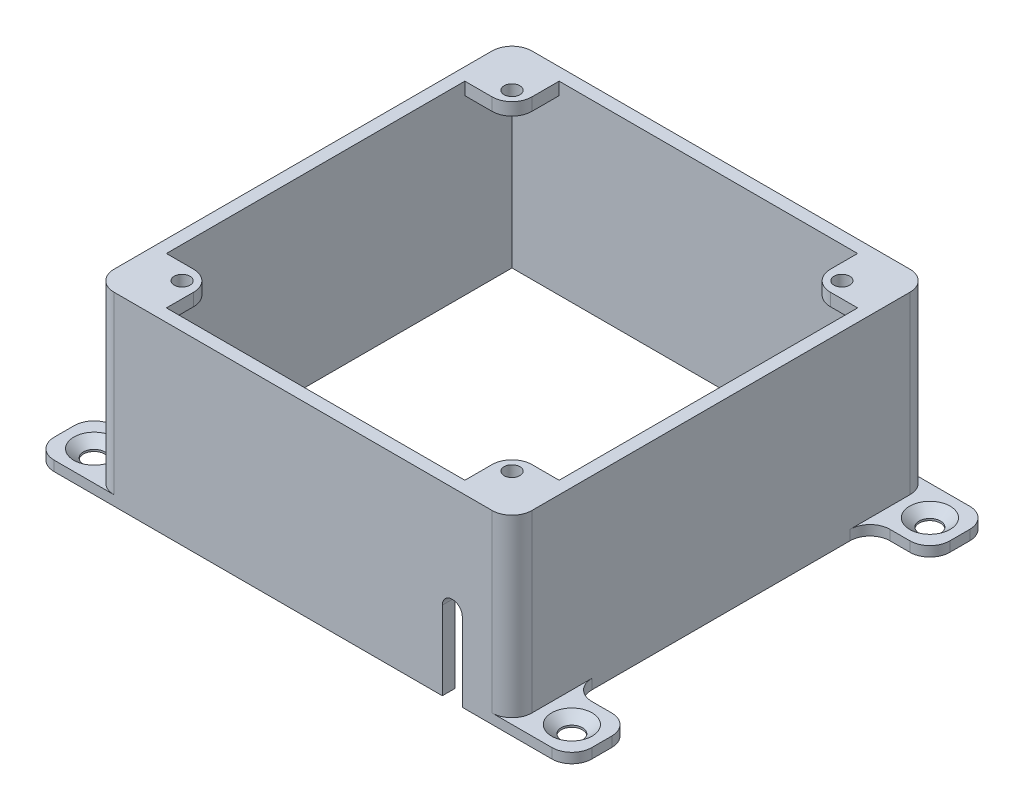
SolidWorks part; units mm, degrees
note: The reader was unsure of these and kept them because the rebuilt part matched: shared geometry of "Sketch1<3>".
ref_plane "Front Plane" through (0, 0, 0) normal (0, 0, 1) x (1, 0, 0)
ref_plane "Top Plane" through (0, 0, 0) normal (0, 1, 0) x (1, 0, 0)
ref_plane "Right Plane" through (0, 0, 0) normal (1, 0, 0) x (0, 0, -1)
sketch "Sketch1" plane through (0, 0, 0) normal (0, 1, 0) x (1, 0, 0)
  line L0 (66.5, 66.5) -> (-66.5, 66.5)
  line L1 (62.5, -62.5) -> (-62.5, -62.5)
  line L2 (62.5, -62.5) -> (62.5, 62.5)
  line L3 (62.5, 62.5) -> (-62.5, 62.5)
  line L4 (-62.5, -62.5) -> (-62.5, 62.5)
  line L5 (62.5, -62.5) -> (-62.5, 62.5) construction
  line L6 (62.5, 62.5) -> (-62.5, -62.5) construction
  line L7 (-66.5, -66.5) -> (-66.5, 66.5)
  line L8 (66.5, -66.5) -> (-66.5, -66.5)
  line L9 (66.5, -66.5) -> (66.5, 66.5)
  line L10 (0, 0) -> (0, 50000) construction
  line L11 (-66.5, 66.5) -> (-85.55, 66.5)
  line L12 (-66.5, 66.5) -> (-66.5, 47.45)
  line L13 (-66.5, 47.45) -> (-85.55, 47.45)
  line L14 (-85.55, 66.5) -> (-85.55, 47.45)
  line L15 (0, 0) -> (50000, 0) construction
  line L16 (66.5, 47.45) -> (85.55, 47.45)
  line L17 (85.55, 66.5) -> (85.55, 47.45)
  line L18 (66.5, 66.5) -> (85.55, 66.5)
  line L19 (66.5, 66.5) -> (66.5, 47.45)
  line L20 (66.5, -66.5) -> (85.55, -66.5)
  line L21 (85.55, -66.5) -> (85.55, -47.45)
  line L22 (66.5, -47.45) -> (85.55, -47.45)
  line L23 (66.5, -66.5) -> (66.5, -47.45)
  line L24 (-66.5, -47.45) -> (-85.55, -47.45)
  line L25 (-85.55, -66.5) -> (-85.55, -47.45)
  line L26 (-66.5, -66.5) -> (-85.55, -66.5)
  line L27 (-66.5, -66.5) -> (-66.5, -47.45)
  point P0 (0, 0)
  dimension "D1" = 125
  dimension "D3" = 19.05
  dimension "D4" = 19.05
  dimension "D2" = 4
extrude "Boss-Extrude1" add sketch "Sketch1" along normal blind 55 contours L8 L9 L0 L7 L1 L4 L3 L2
extrude "Boss-Extrude2" add sketch "Sketch1<3>" along normal blind 3.175 contours L11 L14 L13 L7 | L26 L7 L24 L25 | L22 L9 L20 L21 | L18 L9 L16 L17
sketch "Sketch1<3>" plane through (0, 0, 0) normal (0, 1, 0) x (1, 0, 0) same geometry as "Sketch1"
sketch "Sketch2" plane through (0, 55, 0) normal (0, 1, 0) x (1, 0, 0)
  line L0 (0, 0) -> (0, 50000) construction
  line L1 (-62.5, 62.5) -> (-47.5, 62.5) construction
  line L2 (-62.5, 62.5) -> (-62.5, 47.5) construction
  line L3 (-62.5, 47.5) -> (-47.5, 47.5)
  line L4 (-47.5, 62.5) -> (-47.5, 47.5)
  line L5 (0, 0) -> (50000, 0) construction
  line L6 (62.5, 47.5) -> (47.5, 47.5)
  line L7 (47.5, 62.5) -> (47.5, 47.5)
  line L8 (62.5, 62.5) -> (47.5, 62.5) construction
  line L9 (62.5, 62.5) -> (62.5, 47.5) construction
  line L10 (62.5, -62.5) -> (62.5, -47.5) construction
  line L11 (62.5, -62.5) -> (47.5, -62.5) construction
  line L12 (47.5, -62.5) -> (47.5, -47.5)
  line L13 (62.5, -47.5) -> (47.5, -47.5)
  line L14 (-62.5, -47.5) -> (-47.5, -47.5)
  line L15 (-47.5, -62.5) -> (-47.5, -47.5)
  line L16 (-62.5, -62.5) -> (-47.5, -62.5) construction
  line L17 (-62.5, -62.5) -> (-62.5, -47.5) construction
  line L18 (-62.5, 47.5) -> (-62.5, -47.5)
  line L19 (52.5, -52.5) -> (-52.5, -52.5) construction
  line L20 (52.5, -52.5) -> (52.5, 52.5) construction
  line L21 (52.5, 52.5) -> (-52.5, 52.5) construction
  line L22 (-52.5, -52.5) -> (-52.5, 52.5) construction
  line L23 (52.5, -52.5) -> (-52.5, 52.5) construction
  line L24 (52.5, 52.5) -> (-52.5, -52.5) construction
  line L25 (-47.5, -62.5) -> (47.5, -62.5)
  line L26 (62.5, -47.5) -> (62.5, 47.5)
  line L27 (47.5, 62.5) -> (-47.5, 62.5)
  line L28 (66.5, -66.5) -> (66.5, 66.5) construction
  line L29 (66.5, -66.5) -> (-66.5, -66.5) construction
  line L30 (-66.5, -66.5) -> (-66.5, 66.5) construction
  line L31 (66.5, 66.5) -> (-66.5, 66.5) construction
  line L32 (66.5, -66.5) -> (66.5, 66.5)
  line L33 (66.5, -66.5) -> (-66.5, -66.5)
  line L34 (-66.5, -66.5) -> (-66.5, 66.5)
  line L35 (66.5, 66.5) -> (-66.5, 66.5)
  circle A0 centre (-52.5, 52.5) radius 2.5
  circle A1 centre (52.5, 52.5) radius 2.5
  circle A2 centre (52.5, -52.5) radius 2.5
  circle A3 centre (-52.5, -52.5) radius 2.5
  point P22 (0, 0)
  dimension "D3" = 5
  dimension "D1" = 15
  dimension "D2" = 105
extrude "Boss-Extrude3" add sketch "Sketch2" along normal blind 4 contours L3 L4 L27 L7 L6 L26 L13 L12 L25 L15 L14 L18
sketch "Sketch3" plane through (0, 3.175, 0) normal (0, 1, 0) x (1, 0, 0)
  line L0 (-85.55, -56.975) -> (49914.45, -56.975) construction
  line L1 (-85.55, -66.5) -> (-85.55, -47.45) construction
  line L2 (-76.025, -47.45) -> (-76.025, -50047.45) construction
  line L3 (-66.5, -47.45) -> (-85.55, -47.45) construction
  point P4 (-85.55, -56.975)
  point P10 (-76.025, -56.975)
  point P13 (-76.025, -47.45)
hole_wizard "CSK for 1/4 Flat Head Machine Screw (100)1" positions "Sketch3" profile "Sketch5" countersink size "1/4" standard "ANSI Inch"
sketch "Sketch5" plane through (-76.025, 3.175, 56.975) normal (1, 0, 0) x (0, 0, 1)
  line L0 (0, 0) -> (0, 3.175)
  line L1 (0, 3.175) -> (3.3782, 3.175)
  line L2 (3.3782, 3.175) -> (3.3782, 2.5682)
  line L3 (3.3782, 2.5682) -> (6.4389, 0)
  line L5 (6.4389, 0) -> (0, 0)
  line L6 (-3.3782, 2.5682) -> (-6.4389, 0) construction
  line L11 (0, -6.35) -> (0, 107.95) construction
  dimension "Thru Hole Dia." = 6.7564
  dimension "Thru Hole Depth" = 3.175
  dimension "Near C'Sink Dia." = 12.8778
  dimension "Near C'Sink Angle" = 100
mirror "Mirror1" about plane through (0, 0, 0) normal (0, 0, 1) of "CSK for 1/4 Flat Head Machine Screw (100)1" second plane through (0, 0, 0) second plane normal (1, 0, 0)
fillet "Fillet1" radius 6.35 20 edges at (66.5, 31.0875, 66.5) (66.5, 1.5875, -47.45) (85.55, 1.5875, -47.45) (85.55, 1.5875, -66.5) (85.55, 1.5875, 66.5) (85.55, 1.5875, 47.45) (66.5, 1.5875, 47.45) (47.5, 57, 47.5) (-47.5, 57, 47.5) (-47.5, 57, -47.5) (47.5, 57, -47.5) (66.5, 31.0875, -66.5) (-66.5, 31.0875, 66.5) (-66.5, 31.0875, -66.5) (-66.5, 1.5875, 47.45) (-66.5, 1.5875, -47.45) (-85.55, 1.5875, 66.5) (-85.55, 1.5875, 47.45) (-85.55, 1.5875, -47.45) (-85.55, 1.5875, -66.5)
sketch "Sketch6" plane through (0, 0, 66.5) normal (0, 0, 1) x (1, 0, 0)
  line L0 (47.5, 0) -> (47.5, 25) construction
  line L1 (79.2, 0) -> (-79.2, 0) construction
  line L2 (44.325, 0) -> (44.325, 25)
  line L3 (50.675, 0) -> (50.675, 25)
  arc A0 (44.325, 0) -> (50.675, 0) centre (47.5, 0) ccw
  arc A1 (50.675, 25) -> (44.325, 25) centre (47.5, 25) ccw
  point P4 (47.5, 12.5)
  dimension "D1" = 6.35
  dimension "D2" = 15
  dimension "D3" = 25
extrude "Cut-Extrude1" cut sketch "Sketch6" against normal up to surface (4 mm away) up to face at (0, 42.25, 62.5)
